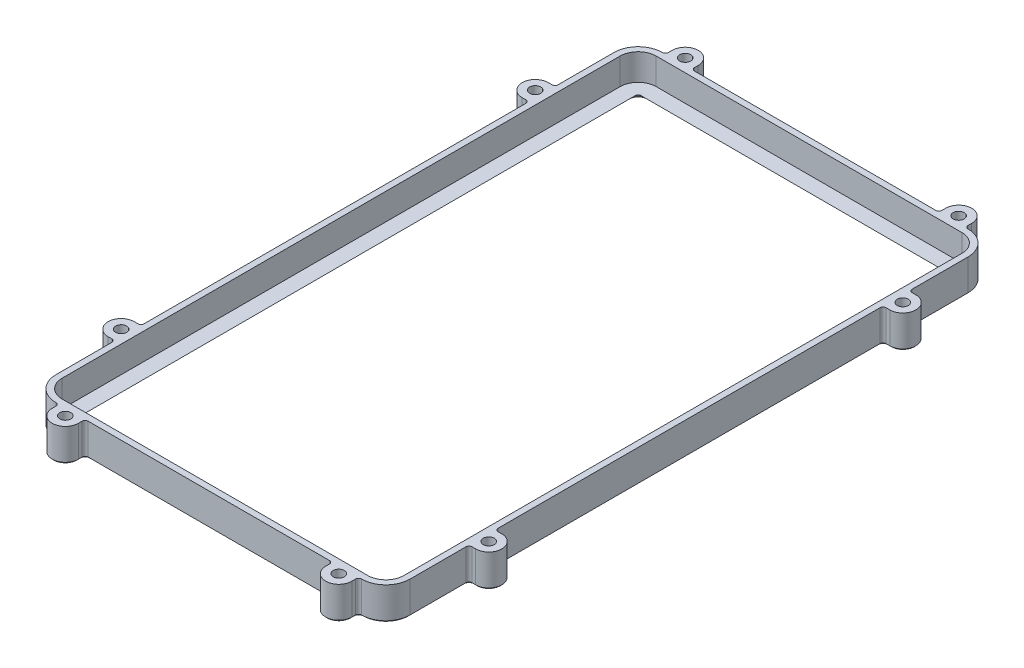
SolidWorks part; units mm, degrees
ref_plane "Front Plane" through (0, 0, 0) normal (0, 0, 1) x (1, 0, 0)
ref_plane "Top Plane" through (0, 0, 0) normal (0, 1, 0) x (1, 0, 0)
ref_plane "Right Plane" through (0, 0, 0) normal (1, 0, 0) x (0, 0, -1)
sketch "Sketch19" plane through (0, 0, 0) normal (0, 1, 0) x (-1, 0, 0)
  line L1 (-6.5603, 45.4694) -> (93.0397, 45.4694)
  line L2 (-14.4403, 37.5894) -> (-14.4403, -144.2106)
  line L3 (-6.5603, -152.0906) -> (93.0397, -152.0906)
  line L4 (100.9197, 37.5894) -> (100.9197, -144.2106)
  arc A0 (-14.4403, -144.2106) -> (-6.5603, -152.0906) centre (-6.5603, -144.2106) ccw
  arc A1 (93.0397, -152.0906) -> (100.9197, -144.2106) centre (93.0397, -144.2106) ccw
  arc A2 (100.9197, 37.5894) -> (93.0397, 45.4694) centre (93.0397, 37.5894) ccw
  arc A3 (-6.5603, 45.4694) -> (-14.4403, 37.5894) centre (-6.5603, 37.5894) ccw
  point P5 (0, 0)
  point P7 (-14.4403, -152.0906)
  point P12 (100.9197, 45.4694)
  point P15 (-14.4403, 45.4694)
  dimension "D5" = 7.88
  dimension "D3" = 115.36
  dimension "D4" = 197.56
extrude "Base" add sketch "Sketch19" along normal blind 10.64
shell "Shell" thickness 2 removed face at (-43.2397, 0, -53.3106) removed face at (-43.2397, 10.64, -53.3106)
sketch "Sketch22" plane through (0, 0, 0) normal (0, -1, 0) x (-1, 0, 0)
  line L0 (-5.5603, 154.2906) -> (-5.5603, 152.0906)
  line L1 (-6.5603, 152.0906) -> (93.0397, 152.0906) construction
  line L2 (-5.5603, 152.0906) -> (2.9397, 152.0906)
  line L3 (2.9397, 152.0906) -> (2.9397, 154.2906)
  line L4 (83.5397, 154.2906) -> (83.5397, 152.0906)
  line L5 (83.5397, 152.0906) -> (92.0397, 152.0906)
  line L6 (92.0397, 152.0906) -> (92.0397, 154.2906)
  line L7 (-5.5603, -47.6694) -> (-5.5603, -45.4694)
  line L8 (93.0397, -45.4694) -> (-6.5603, -45.4694) construction
  line L9 (-5.5603, -45.4694) -> (2.9397, -45.4694)
  line L10 (2.9397, -45.4694) -> (2.9397, -47.6694)
  line L11 (83.5397, -47.6694) -> (83.5397, -45.4694)
  line L12 (83.5397, -45.4694) -> (92.0397, -45.4694)
  line L13 (92.0397, -45.4694) -> (92.0397, -47.6694)
  line L14 (-14.4403, -37.5894) -> (-14.4403, 144.2106) construction
  line L15 (100.9197, 144.2106) -> (100.9197, -37.5894) construction
  line L16 (-14.4403, 53.3106) -> (100.9197, 53.3106) construction
  line L17 (-16.6403, -18.3894) -> (-14.4403, -18.3894)
  line L18 (-14.4403, -18.3894) -> (-14.4403, -9.8894)
  line L19 (-14.4403, -9.8894) -> (-16.6403, -9.8894)
  line L20 (-16.6403, 116.5106) -> (-14.4403, 116.5106)
  line L21 (-14.4403, 116.5106) -> (-14.4403, 125.0106)
  line L22 (-14.4403, 125.0106) -> (-16.6403, 125.0106)
  line L23 (103.1197, 125.0106) -> (100.9197, 125.0106)
  line L24 (100.9197, 125.0106) -> (100.9197, 116.5106)
  line L25 (100.9197, 116.5106) -> (103.1197, 116.5106)
  line L26 (100.9197, -9.8894) -> (103.1197, -9.8894)
  line L27 (100.9197, -9.8894) -> (100.9197, -18.3894)
  line L28 (100.9197, -18.3894) -> (103.1197, -18.3894)
  arc A0 (-5.5603, 154.2906) -> (2.9397, 154.2906) centre (-1.3103, 154.2906) cw
  arc A1 (83.5397, 154.2906) -> (92.0397, 154.2906) centre (87.7897, 154.2906) cw
  arc A2 (-5.5603, -47.6694) -> (2.9397, -47.6694) centre (-1.3103, -47.6694) ccw
  arc A3 (83.5397, -47.6694) -> (92.0397, -47.6694) centre (87.7897, -47.6694) ccw
  arc A4 (-16.6403, 125.0106) -> (-16.6403, 116.5106) centre (-16.6403, 120.7606) ccw
  arc A5 (103.1197, 125.0106) -> (103.1197, 116.5106) centre (103.1197, 120.7606) cw
  arc A6 (103.1197, -9.8894) -> (103.1197, -18.3894) centre (103.1197, -14.1394) cw
  arc A7 (-16.6403, -9.8894) -> (-16.6403, -18.3894) centre (-16.6403, -14.1394) ccw
  dimension "D1" = 8.88
  dimension "D2" = 8.88
  dimension "D3" = 2.2
  dimension "D4" = 8.5
  dimension "D5" = 63.2
  dimension "D6" = 63.2
extrude "Clamps" add sketch "Sketch22" against normal up to surface (10.64 mm away) up to face at (-43.2397, 10.64, -53.3106)
fillet "Clamp Fillets" radius 1 16 edges at (-83.5397, 5.32, 45.4694) (5.5603, 5.32, 45.4694) (-2.9397, 5.32, 45.4694) (-92.0397, 5.32, 45.4694) (-2.9397, 5.32, -152.0906) (-92.0397, 5.32, -152.0906) (-83.5397, 5.32, -152.0906) (5.5603, 5.32, -152.0906) (-100.9197, 5.32, 18.3894) (-100.9197, 5.32, -116.5106) (-100.9197, 5.32, -125.0106) (-100.9197, 5.32, 9.8894) (14.4403, 5.32, -125.0106) (14.4403, 5.32, 9.8894) (14.4403, 5.32, -116.5106) (14.4403, 5.32, 18.3894)
sketch "Sketch25" plane through (0, 0, 0) normal (0, -1, 0) x (1, 0, 0)
  line L24 (14.4403, -144.2106) -> (14.4403, -126.0106)
  line L25 (5.5603, 46.4694) -> (5.5603, 47.6694)
  line L26 (-2.9397, 47.6694) -> (-2.9397, 46.4694)
  line L27 (-3.9397, 45.4694) -> (-82.5397, 45.4694)
  line L28 (-83.5397, 46.4694) -> (-83.5397, 47.6694)
  line L29 (-92.0397, 47.6694) -> (-92.0397, 46.4694)
  line L30 (-100.9197, 37.5894) -> (-100.9197, 19.3894)
  line L31 (-92.0397, -153.0906) -> (-92.0397, -154.2906)
  line L32 (-83.5397, -154.2906) -> (-83.5397, -153.0906)
  line L33 (-82.5397, -152.0906) -> (-3.9397, -152.0906)
  line L34 (-2.9397, -153.0906) -> (-2.9397, -154.2906)
  line L35 (5.5603, -154.2906) -> (5.5603, -153.0906)
  line L36 (14.4403, -144.2106) -> (14.4403, -126.0106)
  line L37 (5.5603, 46.4694) -> (5.5603, 47.6694)
  line L38 (-2.9397, 47.6694) -> (-2.9397, 46.4694)
  line L39 (-3.9397, 45.4694) -> (-82.5397, 45.4694)
  line L40 (-83.5397, 46.4694) -> (-83.5397, 47.6694)
  line L41 (-92.0397, 47.6694) -> (-92.0397, 46.4694)
  line L42 (-100.9197, 37.5894) -> (-100.9197, 19.3894)
  line L43 (-92.0397, -153.0906) -> (-92.0397, -154.2906)
  line L44 (-83.5397, -154.2906) -> (-83.5397, -153.0906)
  line L45 (-82.5397, -152.0906) -> (-3.9397, -152.0906)
  line L46 (-2.9397, -153.0906) -> (-2.9397, -154.2906)
  line L47 (5.5603, -154.2906) -> (5.5603, -153.0906)
  line L48 (6.5603, 38.4694) -> (-93.0397, 38.4694)
  line L49 (-93.9197, 37.5894) -> (-93.9197, -144.2106)
  line L50 (7.4403, -144.2106) -> (7.4403, 37.5894)
  line L51 (-93.0397, -145.0906) -> (6.5603, -145.0906)
  line L52 (6.5603, 38.4694) -> (-93.0397, 38.4694)
  line L53 (-93.9197, 37.5894) -> (-93.9197, -144.2106)
  line L54 (7.4403, -144.2106) -> (7.4403, 37.5894)
  line L55 (-93.0397, -145.0906) -> (6.5603, -145.0906)
  line L60 (15.4403, -125.0106) -> (16.6403, -125.0106)
  line L61 (15.4403, -125.0106) -> (16.6403, -125.0106)
  line L62 (16.6403, -116.5106) -> (15.4403, -116.5106)
  line L63 (16.6403, -116.5106) -> (15.4403, -116.5106)
  line L64 (14.4403, -115.5106) -> (14.4403, 8.8894)
  line L66 (15.4403, 9.8894) -> (16.6403, 9.8894)
  line L67 (15.4403, 9.8894) -> (16.6403, 9.8894)
  line L68 (16.6403, 18.3894) -> (15.4403, 18.3894)
  line L69 (16.6403, 18.3894) -> (15.4403, 18.3894)
  line L70 (14.4403, 19.3894) -> (14.4403, 37.5894)
  line L71 (14.4403, 19.3894) -> (14.4403, 37.5894)
  line L72 (-101.9197, 18.3894) -> (-103.1197, 18.3894)
  line L73 (-101.9197, 18.3894) -> (-103.1197, 18.3894)
  line L74 (-103.1197, 9.8894) -> (-101.9197, 9.8894)
  line L75 (-103.1197, 9.8894) -> (-101.9197, 9.8894)
  line L76 (14.4403, -115.5106) -> (14.4403, 8.8894)
  line L78 (-101.9197, -116.5106) -> (-103.1197, -116.5106)
  line L79 (-101.9197, -116.5106) -> (-103.1197, -116.5106)
  line L80 (-103.1197, -125.0106) -> (-101.9197, -125.0106)
  line L81 (-103.1197, -125.0106) -> (-101.9197, -125.0106)
  line L82 (-100.9197, -126.0106) -> (-100.9197, -144.2106)
  line L83 (-100.9197, -126.0106) -> (-100.9197, -144.2106)
  line L84 (-100.9197, 8.8894) -> (-100.9197, -115.5106)
  line L85 (-100.9197, 8.8894) -> (-100.9197, -115.5106)
  arc A4 (7.4403, 37.5894) -> (6.5603, 38.4694) centre (6.5603, 37.5894) ccw
  arc A5 (7.4403, 37.5894) -> (6.5603, 38.4694) centre (6.5603, 37.5894) ccw
  arc A6 (-93.0397, 38.4694) -> (-93.9197, 37.5894) centre (-93.0397, 37.5894) ccw
  arc A7 (-93.0397, 38.4694) -> (-93.9197, 37.5894) centre (-93.0397, 37.5894) ccw
  arc A8 (6.5603, -145.0906) -> (7.4403, -144.2106) centre (6.5603, -144.2106) ccw
  arc A9 (6.5603, -145.0906) -> (7.4403, -144.2106) centre (6.5603, -144.2106) ccw
  arc A10 (-93.9197, -144.2106) -> (-93.0397, -145.0906) centre (-93.0397, -144.2106) ccw
  arc A11 (-93.9197, -144.2106) -> (-93.0397, -145.0906) centre (-93.0397, -144.2106) ccw
  arc A24 (5.5603, 46.4694) -> (6.5603, 45.4694) centre (6.5603, 46.4694) ccw
  arc A25 (5.5603, 46.4694) -> (6.5603, 45.4694) centre (6.5603, 46.4694) ccw
  arc A26 (-93.0397, 45.4694) -> (-92.0397, 46.4694) centre (-93.0397, 46.4694) ccw
  arc A27 (-93.0397, 45.4694) -> (-92.0397, 46.4694) centre (-93.0397, 46.4694) ccw
  arc A28 (-92.0397, -153.0906) -> (-93.0397, -152.0906) centre (-93.0397, -153.0906) ccw
  arc A29 (-92.0397, -153.0906) -> (-93.0397, -152.0906) centre (-93.0397, -153.0906) ccw
  arc A30 (6.5603, -152.0906) -> (5.5603, -153.0906) centre (6.5603, -153.0906) ccw
  arc A31 (6.5603, -152.0906) -> (5.5603, -153.0906) centre (6.5603, -153.0906) ccw
  arc A32 (6.5603, -152.0906) -> (14.4403, -144.2106) centre (6.5603, -144.2106) ccw
  arc A33 (14.4403, 37.5894) -> (6.5603, 45.4694) centre (6.5603, 37.5894) ccw
  arc A35 (5.5603, 47.6694) -> (-2.9397, 47.6694) centre (1.3103, 47.6694) ccw
  arc A36 (-3.9397, 45.4694) -> (-2.9397, 46.4694) centre (-3.9397, 46.4694) ccw
  arc A37 (-83.5397, 46.4694) -> (-82.5397, 45.4694) centre (-82.5397, 46.4694) ccw
  arc A38 (-83.5397, 47.6694) -> (-92.0397, 47.6694) centre (-87.7897, 47.6694) ccw
  arc A40 (-93.0397, 45.4694) -> (-100.9197, 37.5894) centre (-93.0397, 37.5894) ccw
  arc A41 (-100.9197, -144.2106) -> (-93.0397, -152.0906) centre (-93.0397, -144.2106) ccw
  arc A43 (-92.0397, -154.2906) -> (-83.5397, -154.2906) centre (-87.7897, -154.2906) ccw
  arc A44 (-82.5397, -152.0906) -> (-83.5397, -153.0906) centre (-82.5397, -153.0906) ccw
  arc A45 (-2.9397, -153.0906) -> (-3.9397, -152.0906) centre (-3.9397, -153.0906) ccw
  arc A46 (-2.9397, -154.2906) -> (5.5603, -154.2906) centre (1.3103, -154.2906) ccw
  arc A48 (6.5603, -152.0906) -> (14.4403, -144.2106) centre (6.5603, -144.2106) ccw
  arc A49 (14.4403, 37.5894) -> (6.5603, 45.4694) centre (6.5603, 37.5894) ccw
  arc A51 (5.5603, 47.6694) -> (-2.9397, 47.6694) centre (1.3103, 47.6694) ccw
  arc A52 (-3.9397, 45.4694) -> (-2.9397, 46.4694) centre (-3.9397, 46.4694) ccw
  arc A53 (-83.5397, 46.4694) -> (-82.5397, 45.4694) centre (-82.5397, 46.4694) ccw
  arc A54 (-83.5397, 47.6694) -> (-92.0397, 47.6694) centre (-87.7897, 47.6694) ccw
  arc A56 (-93.0397, 45.4694) -> (-100.9197, 37.5894) centre (-93.0397, 37.5894) ccw
  arc A57 (-100.9197, -144.2106) -> (-93.0397, -152.0906) centre (-93.0397, -144.2106) ccw
  arc A59 (-92.0397, -154.2906) -> (-83.5397, -154.2906) centre (-87.7897, -154.2906) ccw
  arc A60 (-82.5397, -152.0906) -> (-83.5397, -153.0906) centre (-82.5397, -153.0906) ccw
  arc A61 (-2.9397, -153.0906) -> (-3.9397, -152.0906) centre (-3.9397, -153.0906) ccw
  arc A62 (-2.9397, -154.2906) -> (5.5603, -154.2906) centre (1.3103, -154.2906) ccw
  arc A63 (16.6403, -125.0106) -> (16.6403, -116.5106) centre (16.6403, -120.7606) ccw
  arc A64 (16.6403, -125.0106) -> (16.6403, -116.5106) centre (16.6403, -120.7606) ccw
  arc A65 (16.6403, 9.8894) -> (16.6403, 18.3894) centre (16.6403, 14.1394) ccw
  arc A66 (16.6403, 9.8894) -> (16.6403, 18.3894) centre (16.6403, 14.1394) ccw
  arc A67 (-103.1197, 18.3894) -> (-103.1197, 9.8894) centre (-103.1197, 14.1394) ccw
  arc A68 (-103.1197, 18.3894) -> (-103.1197, 9.8894) centre (-103.1197, 14.1394) ccw
  arc A69 (-103.1197, -116.5106) -> (-103.1197, -125.0106) centre (-103.1197, -120.7606) ccw
  arc A70 (-103.1197, -116.5106) -> (-103.1197, -125.0106) centre (-103.1197, -120.7606) ccw
  arc A79 (15.4403, -125.0106) -> (14.4403, -126.0106) centre (15.4403, -126.0106) ccw
  arc A80 (15.4403, -125.0106) -> (14.4403, -126.0106) centre (15.4403, -126.0106) ccw
  arc A81 (14.4403, -115.5106) -> (15.4403, -116.5106) centre (15.4403, -115.5106) ccw
  arc A82 (14.4403, -115.5106) -> (15.4403, -116.5106) centre (15.4403, -115.5106) ccw
  arc A83 (15.4403, 9.8894) -> (14.4403, 8.8894) centre (15.4403, 8.8894) ccw
  arc A84 (15.4403, 9.8894) -> (14.4403, 8.8894) centre (15.4403, 8.8894) ccw
  arc A85 (14.4403, 19.3894) -> (15.4403, 18.3894) centre (15.4403, 19.3894) ccw
  arc A86 (14.4403, 19.3894) -> (15.4403, 18.3894) centre (15.4403, 19.3894) ccw
  arc A87 (-101.9197, 18.3894) -> (-100.9197, 19.3894) centre (-101.9197, 19.3894) ccw
  arc A88 (-101.9197, 18.3894) -> (-100.9197, 19.3894) centre (-101.9197, 19.3894) ccw
  arc A89 (-100.9197, 8.8894) -> (-101.9197, 9.8894) centre (-101.9197, 8.8894) ccw
  arc A90 (-100.9197, 8.8894) -> (-101.9197, 9.8894) centre (-101.9197, 8.8894) ccw
  arc A91 (-101.9197, -116.5106) -> (-100.9197, -115.5106) centre (-101.9197, -115.5106) ccw
  arc A92 (-101.9197, -116.5106) -> (-100.9197, -115.5106) centre (-101.9197, -115.5106) ccw
  arc A93 (-100.9197, -126.0106) -> (-101.9197, -125.0106) centre (-101.9197, -126.0106) ccw
  arc A94 (-100.9197, -126.0106) -> (-101.9197, -125.0106) centre (-101.9197, -126.0106) ccw
  dimension "D1" = 0
  dimension "D2" = 5
extrude "Frame" add sketch "Sketch25" against normal blind 2
chamfer "Frame Chamfer" distance 2 angle 45 8 edges at (-43.2397, 0, 38.4694) (7.4403, 0, -53.3106) (-43.2397, 0, -145.0906) (-93.9197, 0, -53.3106) (7.1825, 0, 38.2116) (7.1825, 0, -144.8329) (-93.662, 0, 38.2116) (-93.662, 0, -144.8329)
sketch "Sketch23" plane through (0, 0, 0) normal (0, -1, 0) x (-1, 0, 0)
  circle A0 centre (-1.3103, 154.2906) radius 1.8
  circle A1 centre (87.7897, 154.2906) radius 1.8
  circle A2 centre (-1.3103, -47.6694) radius 1.8
  circle A3 centre (87.7897, -47.6694) radius 1.8
  arc A4 (2.9397, 154.2906) -> (-5.5603, 154.2906) centre (-1.3103, 154.2906) ccw construction
  arc A5 (92.0397, 154.2906) -> (83.5397, 154.2906) centre (87.7897, 154.2906) ccw construction
  arc A6 (-5.5603, -47.6694) -> (2.9397, -47.6694) centre (-1.3103, -47.6694) ccw construction
  arc A7 (83.5397, -47.6694) -> (92.0397, -47.6694) centre (87.7897, -47.6694) ccw construction
  circle A8 centre (-16.6403, 120.7606) radius 1.8
  circle A9 centre (103.1197, 120.7606) radius 1.8
  circle A10 centre (103.1197, -14.1394) radius 1.8
  circle A11 centre (-16.6403, -14.1394) radius 1.8
  dimension "D1" = 3.6
extrude "Clamp Holes" cut sketch "Sketch23" against normal through all
sketch "Sketch24" plane through (0, 0, 0) normal (0, -1, 0) x (1, 0, 0)
  circle A0 centre (-87.7897, 47.6694) radius 2.9
  circle A1 centre (1.3103, 47.6694) radius 2.9
  circle A2 centre (1.3103, -154.2906) radius 2.9
  circle A3 centre (-87.7897, -154.2906) radius 2.9
  arc A4 (-83.5397, 47.6694) -> (-92.0397, 47.6694) centre (-87.7897, 47.6694) ccw construction
  arc A5 (5.5603, 47.6694) -> (-2.9397, 47.6694) centre (1.3103, 47.6694) ccw construction
  arc A6 (-92.0397, -154.2906) -> (-83.5397, -154.2906) centre (-87.7897, -154.2906) ccw construction
  arc A7 (-2.9397, -154.2906) -> (5.5603, -154.2906) centre (1.3103, -154.2906) ccw construction
  circle A8 centre (16.6403, -120.7606) radius 2.9
  circle A9 centre (-103.1197, -120.7606) radius 2.9
  circle A10 centre (-103.1197, 14.1394) radius 2.9
  circle A11 centre (16.6403, 14.1394) radius 2.9
  dimension "D1" = 5.8
extrude "Clamp Countersinks" cut sketch "Sketch24" against normal blind 3.4
chamfer "Clamp Countersink Chamfers" distance 0.3 angle 45 4 edges at (-87.7897, 0, -157.1906) (1.3103, 0, -157.1906) (1.3103, 0, 44.7694) (-87.7897, 0, 44.7694)
chamfer "Shell Chamfer" distance 0.5 angle 45 52 edges at (-100.9197, 0, 28.4894) (-100.9197, 0, -135.1106) (-98.6117, 0, -149.7826) (-92.3326, 0, -152.3835) (-92.0397, 0, -153.6906) (-87.7897, 0, -158.5406) (-83.5397, 0, -153.6906) (-83.2468, 0, -152.3835) (-43.2397, 0, -152.0906) (-3.2326, 0, -152.3835) (-2.9397, 0, -153.6906) (1.3103, 0, -158.5406) (5.5603, 0, -153.6906) (5.8532, 0, -152.3835) (12.1323, 0, -149.7826) (14.4403, 0, -135.1106) (14.4403, 0, 28.4894) (12.1323, 0, 43.1614) (5.8532, 0, 45.7623) (5.5603, 0, 47.0694) (1.3103, 0, 51.9194) (-2.9397, 0, 47.0694) (-3.2326, 0, 45.7623) (-43.2397, 0, 45.4694) (-83.2468, 0, 45.7623) (-83.5397, 0, 47.0694) (-87.7897, 0, 51.9194) (-92.0397, 0, 47.0694) (-92.3326, 0, 45.7623) (-98.6117, 0, 43.1614) (-101.2126, 0, -125.3035) (14.7332, 0, -125.3035) (-102.5197, 0, -125.0106) (16.0403, 0, -125.0106) (-107.3697, 0, -120.7606) (20.8903, 0, -120.7606) (-102.5197, 0, -116.5106) (16.0403, 0, -116.5106) (-101.2126, 0, -116.2177) (14.7332, 0, -116.2177) (-100.9197, 0, -53.3106) (14.4403, 0, -53.3106) (-101.2126, 0, 9.5965) (14.7332, 0, 9.5965) (-102.5197, 0, 9.8894) (16.0403, 0, 9.8894) (-107.3697, 0, 14.1394) (20.8903, 0, 14.1394) (-102.5197, 0, 18.3894) (16.0403, 0, 18.3894) (-101.2126, 0, 18.6823) (14.7332, 0, 18.6823)
